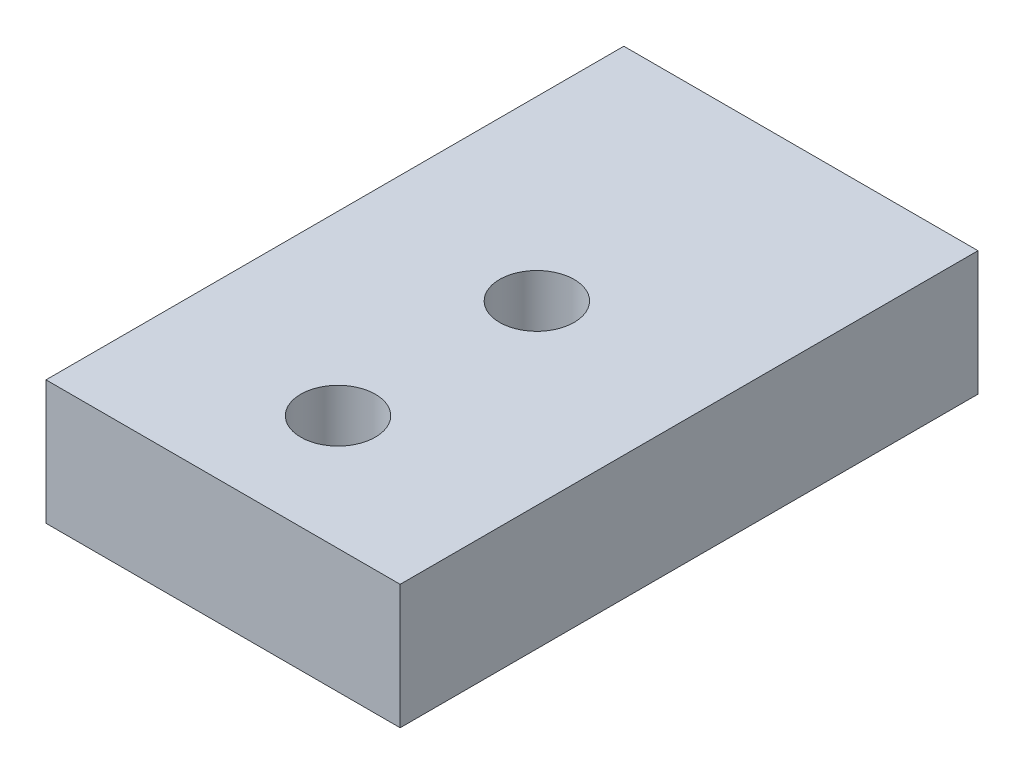
SolidWorks part; units mm, degrees
ref_plane "Front Plane" through (0, 0, 0) normal (0, 0, 1) x (1, 0, 0)
ref_plane "Top Plane" through (0, 0, 0) normal (0, 1, 0) x (1, 0, 0)
ref_plane "Right Plane" through (0, 0, 0) normal (1, 0, 0) x (0, 0, -1)
sketch "Sketch1" plane through (0, 0, 0) normal (0, 1, 0) x (1, 0, 0)
  line L1 (-14.25, 21.25) -> (14.25, 21.25)
  line L2 (-14.25, 21.25) -> (-14.25, -25.25)
  line L3 (-14.25, -25.25) -> (14.25, -25.25)
  line L4 (14.25, 21.25) -> (14.25, -25.25)
  circle A0 centre (0, -16) radius 8 construction
  circle A1 centre (0, 0) radius 8 construction
  circle A2 centre (0, 10) radius 18 construction
  circle A3 centre (0, 0) radius 3
  circle A4 centre (0, -16) radius 3
  point P10 (0, 21.25)
  dimension "D1" = 36
  dimension "D2" = 16
  dimension "D6" = 6
  dimension "D7" = 6
  dimension "D3" = 11.25
  dimension "D4" = 46.5
  dimension "D5" = 28.5
extrude "Boss-Extrude1" add sketch "Sketch1" along normal blind 10
equation "\"drive_gear_pitch_diameter\"= 0.8mm * \"drive_gear_tooth_count\""
equation "\"driven_gear_pitch_diameter\"= 0.8mm * \"driven_gear_tooth_count\""
equation "\"D2@Sketch1\"=\"driven_gear_pitch_diameter\""
equation "\"D1@Sketch1\"=\"drive_gear_pitch_diameter\""
equation "\"drive_gear_tooth_count\"= 45"
equation "\"driven_gear_tooth_count\"= 20"
